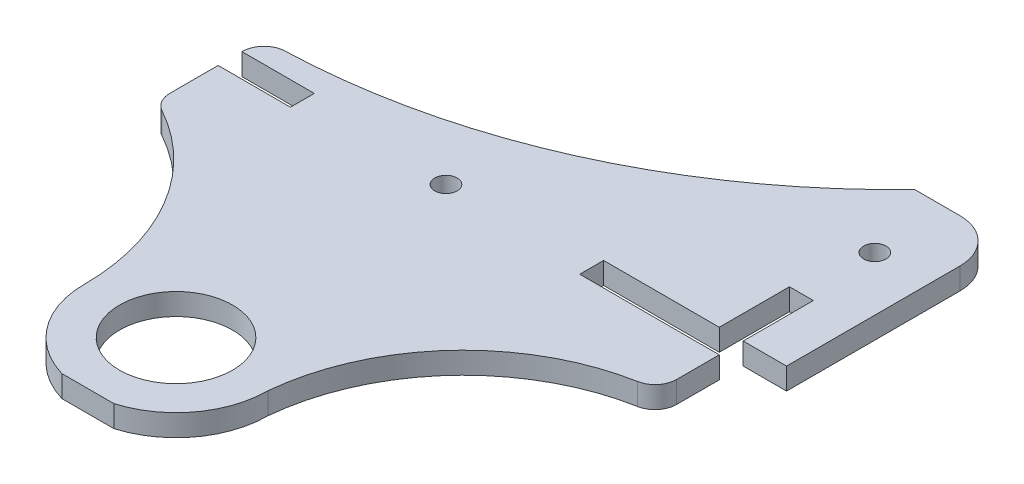
SolidWorks part; units mm, degrees
ref_plane "Alzado" through (0, 0, 0) normal (0, 0, 1) x (1, 0, 0)
ref_plane "Planta" through (0, 0, 0) normal (0, 1, 0) x (1, 0, 0)
ref_plane "Vista lateral" through (0, 0, 0) normal (1, 0, 0) x (0, 0, -1)
sketch "Croquis1" plane through (0, 0, 0) normal (0, 1, 0) x (1, 0, 0)
  line L0 (0, 38.7) -> (69.3, 38.7) construction
  line L1 (0, 0) -> (69.3, 0) construction
  line L2 (0, 0) -> (0, 38.7)
  line L3 (0, 72) -> (69.3, 72)
  line L4 (69.3, 0) -> (69.3, 38.7)
  line L5 (69.3, 51.7) -> (69.3, 72) construction
  line L8 (69.3, 51.7) -> (66, 51.7)
  line L9 (66, 42) -> (66, 51.7)
  line L11 (69.3, 38.7) -> (50, 38.7)
  line L13 (66, 42) -> (50, 42)
  line L14 (50, 38.7) -> (50, 42)
  line L15 (0, 38.7) -> (10, 38.7)
  line L17 (0, 42) -> (10, 42)
  line L18 (10, 38.7) -> (10, 42)
  line L19 (0, 42) -> (0, 72)
  line L20 (69.3, 72) -> (75.3, 72)
  line L21 (69.3, 72) -> (69.3, 51.7) construction
  line L23 (75.3, 72) -> (75.3, 52)
  line L25 (69.3, 51.7) -> (69.3, 42)
  line L26 (69.3, 42) -> (75.3, 42)
  line L27 (75.3, 52) -> (75.3, 42)
  line L28 (0, 0) -> (69.3, 0) construction
  line L29 (0, 0) -> (0, -9)
  line L30 (0, -9) -> (69.3, -9)
  line L31 (69.3, 0) -> (69.3, -9)
  circle A0 centre (30, 40.2) radius 1.55
  circle A1 centre (67.8, 61.7) radius 1.55
  circle A3 centre (29.68, 3.2) radius 7.8109
  dimension "D9" = 3.1
  dimension "D13" = 6
  dimension "D14" = 3.1
  dimension "D18" = 15.6218
  dimension "D2" = 72
  dimension "D3" = 3.3
  dimension "D4" = 13
  dimension "D5" = 16
  dimension "D6" = 3.3
  dimension "D7" = 3.3
  dimension "D8" = 10
  dimension "D10" = 30
  dimension "D11" = 20
  dimension "D12" = 1.5
  dimension "D15" = 1.5
  dimension "D16" = 10
  dimension "D17" = 40
  dimension "D19" = 35.5
  dimension "D20" = 29.68
  dimension "D21" = 30
  dimension "D22" = 9
extrude "Saliente-Extruir10" add sketch "Croquis1" along normal blind 3
sketch "Croquis3" plane through (0, 3, 0) normal (0, 1, 0) x (1, 0, 0)
  line L0 (0, 38.7) -> (0, -9) construction
  line L1 (0, 72) -> (63, 72)
  line L2 (0, 72) -> (0, 45)
  line L5 (10, 38.7) -> (0, 38.7) construction
  line L6 (69.3, -9) -> (69.3, 38.7) construction
  line L7 (69.3, 38.7) -> (50, 38.7) construction
  line L8 (0, -9) -> (69.3, -9) construction
  line L9 (69.3, -9) -> (69.3, 30.2)
  line L10 (0, -9) -> (69.3, -9)
  line L11 (0, 30.2) -> (0, -9)
  arc A0 (42.4, 3.2) -> (69.3, 30.2) centre (72.264, 0.3468) cw
  arc A1 (63, 72) -> (0, 45) centre (0, 132) cw
  arc A4 (16.96, 3.2) -> (42.4, 3.2) centre (29.68, 3.2) ccw
  arc A5 (16.96, 3.2) -> (0, 30.2) centre (-13.04, 3.1823) ccw
  circle M22 centre (67.8, 61.7) radius 1.55
  line M23 (0, 38.7) -> (0, -9)
  line M24 (0, -9) -> (69.3, -9)
  line M25 (69.3, -9) -> (69.3, 38.7)
  line M26 (69.3, 38.7) -> (50, 38.7)
  line M27 (50, 38.7) -> (50, 42)
  line M28 (50, 42) -> (66, 42)
  line M29 (66, 42) -> (66, 51.7)
  line M30 (66, 51.7) -> (69.3, 51.7)
  line M31 (69.3, 51.7) -> (69.3, 42)
  line M32 (69.3, 42) -> (75.3, 42)
  line M33 (75.3, 42) -> (75.3, 72)
  line M34 (75.3, 72) -> (0, 72)
  line M35 (0, 72) -> (0, 42)
  line M36 (0, 42) -> (10, 42)
  line M37 (10, 42) -> (10, 38.7)
  line M38 (10, 38.7) -> (0, 38.7)
  circle M39 centre (30, 40.2) radius 1.55
  dimension "D1" = 30
  dimension "D2" = 25.44
  dimension "D4" = 30
  dimension "D3" = 8.5
  dimension "D5" = 8.5
extrude "Cortar-Extruir2" cut sketch "Croquis3" against normal up to surface (3 mm away) flip side to cut contours A1 M25 M26 M27 M28 M29 M30 M31 M32 M33 M34 M35 M36 M37 M38 M23 M24 M22 M39 region at (38.7129, 3, -32.8125) up to face at (42.4875, 0, -39.7625)
fillet "Redondeo1" radius 6 1 edges at (75.3, 1.5, -72)
fillet "Redondeo2" radius 3 3 edges at (0, 1.5, -45) (69.3, 1.5, -30.2) (0, 1.5, -30.2)
